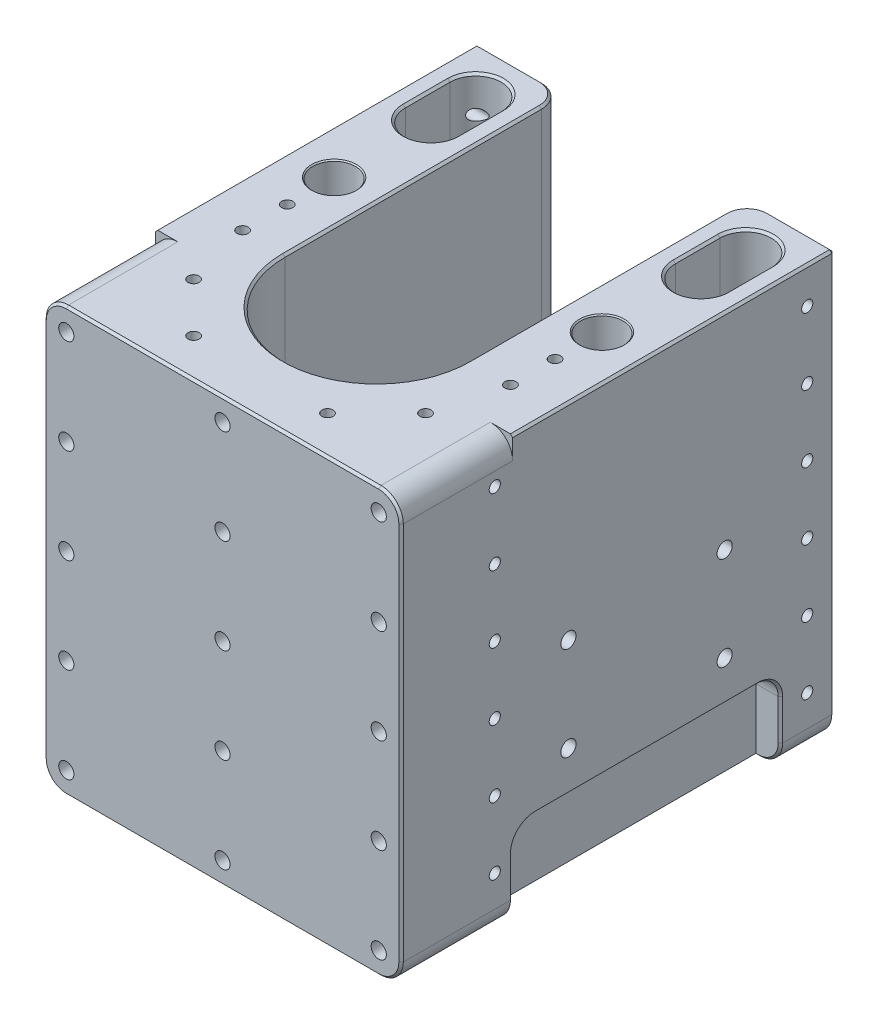
SolidWorks part; units mm, degrees
material "6061-T6 Aluminum"
ref_plane "Front Plane" through (0, 0, 0) normal (0, 0, 1) x (1, 0, 0)
ref_plane "Top Plane" through (0, 0, 0) normal (0, 1, 0) x (1, 0, 0)
ref_plane "Right Plane" through (0, 0, 0) normal (1, 0, 0) x (0, 0, -1)
sketch "Sketch1" plane through (0, 0, 0) normal (0, 1, 0) x (1, 0, 0)
  line L0 (41, 97) -> (80, 97)
  line L1 (-80, -97) -> (80, -97)
  line L2 (-80, -97) -> (-80, 97)
  line L3 (-80, 97) -> (-41, 97)
  line L4 (80, -97) -> (80, 97)
  line L5 (-41, 97) -> (0, 97) construction
  line L6 (0, 97) -> (41, 97) construction
  line L7 (-41, 97) -> (-41, -28)
  line L9 (41, -28) -> (41, 97)
  line L10 (-80, 0) -> (0, 0) construction
  line L11 (0, 0) -> (80, 0) construction
  line L12 (0, -69) -> (0, -97) construction
  arc A2 (-41, -28) -> (41, -28) centre (0, -28) ccw
  point P0 (0, 0)
  dimension "D1" = 160
  dimension "D2" = 194
  dimension "D3" = 28
  dimension "D4" = 82
extrude "Boss-Extrude1" add sketch "Sketch1" along normal blind 190
sketch "Sketch3" plane through (0, 190, 0) normal (0, 1, 0) x (1, 0, 0)
  line L0 (0, 0) -> (0, 13) construction
  line L3 (-60, 13) -> (60, 13) construction
  circle A4 centre (-60, 13) radius 9.55
  circle A5 centre (60, 13) radius 9.55
  dimension "D1" = 13
  dimension "D2" = 120
  dimension "D3" = 19.1
extrude "Cut-Extrude2" cut sketch "Sketch3" against normal blind 20 contours A4 | A5 region at (-60, 190, -13) region at (60, 190, -13)
sketch "Sketch8" plane through (80, 0, 0) normal (1, 0, 0) x (0, 0, -1)
  arc A0 (48, 102.25) -> (48, 93.75) centre (48, 98) ccw construction
  arc A1 (-22, 102.25) -> (-22, 93.75) centre (-22, 98) ccw construction
  arc A2 (-22, 60.25) -> (-22, 51.75) centre (-22, 56) ccw construction
  arc A3 (48, 60.25) -> (48, 51.75) centre (48, 56) ccw construction
  arc A4 (48, 102.25) -> (48, 93.75) centre (48, 98) ccw construction
  arc A5 (-22, 102.25) -> (-22, 93.75) centre (-22, 98) ccw construction
  arc A6 (-22, 60.25) -> (-22, 51.75) centre (-22, 56) ccw construction
  arc A7 (48, 60.25) -> (48, 51.75) centre (48, 56) ccw construction
hole_wizard "M8x1.25 Tapped Hole1" positions "Sketch11" profile "Sketch10" tap size "M8x1.25" standard "ANSI Metric"
sketch "Sketch11" plane through (80, 0, 0) normal (1, 0, 0) x (0, 0, -1)
  point P0 (48, 56)
  point P3 (-22, 56)
  point P6 (-22, 98)
  point P9 (48, 98)
cosmetic thread "Hole Thread2" parameters "D1"=25, "D2"=8
cosmetic thread "Hole Thread3" parameters "D1"=25, "D2"=8
cosmetic thread "Hole Thread4" parameters "D1"=25, "D2"=8
cosmetic thread "Hole Thread5" parameters "D1"=25, "D2"=8
sketch "Sketch10" plane through (80, 56, -48) normal (0, 1, 0) x (0, 0, -1)
  line L0 (0, 0) -> (0, 32.0429)
  line L1 (0, 32.0429) -> (3.4, 30)
  line L2 (3.4, 30) -> (3.4, 0)
  line L5 (3.4, 0) -> (0, 0)
  line L10 (0, 32.0429) -> (-3.4, 30) construction
  line L11 (0, -6.35) -> (0, 107.95) construction
  dimension "Tap Drill Dia." = 6.8
  dimension "Tap Drill Depth" = 30
  dimension "Drill Angle" = 118
mirror "Mirror2" about plane through (0, 0, 0) normal (1, 0, 0) of "M8x1.25 Tapped Hole1"
sketch "Sketch33" plane through (0, 0, 97) normal (0, 0, 1) x (1, 0, 0)
  line L0 (-80, 190) -> (-80, 0) construction
  line L1 (-70, 0) -> (70, 0)
  line L2 (-80, 10) -> (-80, 180)
  line L3 (-70, 190) -> (70, 190)
  line L4 (80, 10) -> (80, 180)
  line L5 (-70, 137.5) -> (-70, 95) construction
  line L6 (-70, 180) -> (-70, 137.5) construction
  line L7 (-70, 95) -> (-70, 52.5) construction
  line L8 (-70, 52.5) -> (-70, 10) construction
  line L9 (-80, 190) -> (80, 190) construction
  arc A0 (-70, 0) -> (-80, 10) centre (-70, 10) cw
  arc A1 (70, 0) -> (80, 10) centre (70, 10) ccw
  arc A2 (70, 190) -> (80, 180) centre (70, 180) cw
  arc A3 (-80, 180) -> (-70, 190) centre (-70, 180) cw
  circle A4 centre (-70, 180) radius 3.375
  circle A5 centre (-70, 137.5) radius 3.375
  circle A7 centre (-70, 95) radius 3.375
  circle A8 centre (-70, 10) radius 3.375
  circle A9 centre (-70, 52.5) radius 3.375
  circle A10 centre (0, 180) radius 3.375
  circle A11 centre (70, 180) radius 3.375
  circle A12 centre (0, 137.5) radius 3.375
  circle A13 centre (70, 137.5) radius 3.375
  circle A14 centre (0, 95) radius 3.375
  circle A15 centre (70, 95) radius 3.375
  circle A16 centre (0, 52.5) radius 3.375
  circle A17 centre (70, 52.5) radius 3.375
  circle A18 centre (70, 10) radius 3.375
  circle A19 centre (0, 10) radius 3.375
  point P5 (-80, 128)
  dimension "D2" = 10
  dimension "D3" = 6.75
fillet "Fillet1" radius 10 2 edges at (41, 95, -97) (-41, 95, -97)
sketch "Sketch36" plane through (0, 0, 0) normal (0, 1, 0) x (1, 0, 0)
  line L0 (-69, 13) -> (0, 13) construction
  line L1 (-102.762, 73) -> (-69, 73)
  line L2 (-102.762, 73) -> (-102.762, -47)
  line L3 (-102.762, -47) -> (-69, -47)
  line L4 (-69, 73) -> (-69, -47)
  line L5 (122.5295, 73) -> (69, 73)
  line L6 (122.5295, 73) -> (122.5295, -47)
  line L7 (122.5295, -47) -> (69, -47)
  line L8 (69, 73) -> (69, -47)
  line L9 (0, 13) -> (69, 13) construction
  line L10 (-80, -18.6) -> (-80, -25.4) construction
  line L11 (-80, 51.4) -> (-80, 44.6) construction
  line L12 (-80, -18.6) -> (-80, -25.4) construction
  line L13 (-80, 51.4) -> (-80, 44.6) construction
  line L14 (-80, 44.6) -> (-69, 13) construction
  line L15 (-69, 13) -> (-80, -18.6) construction
  line L16 (0, 13) -> (0, 0) construction
  dimension "D1" = 138
  dimension "D2" = 120
extrude "Cut-Extrude3" cut sketch "Sketch36" along normal blind 38
hole_wizard "CBORE for M8 SHCS1" positions "Sketch31" profile "Sketch32" counterbore size "M8" standard "ANSI Metric" end condition through all
sketch "Sketch31" plane through (0, 0, 0) normal (0, -1, 0) x (-1, 0, 0)
  circle A4 centre (60, 13) radius 9.55 construction
  circle A5 centre (-60, 13) radius 9.55 construction
  point P0 (60, 13)
  point P2 (-60, 13)
sketch "Sketch32" plane through (-60, 0, -13) normal (1, 0, 0) x (0, 0, -1)
  line L0 (0, 0) -> (0, 190)
  line L1 (0, 190) -> (4.5, 190)
  line L3 (4.5, 190) -> (4.5, 9)
  line L4 (4.5, 9) -> (7.5, 9)
  line L5 (7.5, 9) -> (7.5, 0)
  line L7 (7.5, 0) -> (0, 0)
  line L11 (0, -6.35) -> (0, 107.95) construction
  dimension "Thru Hole Dia." = 9
  dimension "Thru Hole Depth" = 190
  dimension "C'Bore Dia." = 15
  dimension "C'Bore Depth" = 9
chamfer "Chamfer7" distance 0.5 angle 45 2 edges at (60, 190, -3.45) (-60, 190, -3.45)
chamfer "Chamfer11" distance 1 angle 45 2 edges at (60, 0, -20.5) (-60, 0, -20.5)
chamfer "Chamfer12" distance 0.5 angle 45 4 edges at (-60, 9, -17.5) (60, 9, -17.5) (-60, 170, -8.5) (60, 170, -8.5)
sketch "Sketch38" plane through (0, 0, 0) normal (0, -1, 0) x (1, 0, 0)
  circle A0 centre (54, 32.5) radius 4.25 construction
  circle A1 centre (54, 2.5) radius 4.25 construction
  circle A2 centre (54, -27.5) radius 4.25 construction
  circle A3 centre (54, -57.5) radius 4.25 construction
  circle A4 centre (-54, -57.5) radius 4.25 construction
  circle A5 centre (-54, -27.5) radius 4.25 construction
  circle A6 centre (-54, 2.5) radius 4.25 construction
  circle A7 centre (-54, 32.5) radius 4.25 construction
  circle A8 centre (54, 32.5) radius 4.25
  circle A9 centre (54, 2.5) radius 4.25
  circle A10 centre (54, -27.5) radius 4.25
  circle A11 centre (54, -57.5) radius 4.25
  circle A12 centre (-54, -57.5) radius 4.25
  circle A13 centre (-54, -27.5) radius 4.25
  circle A14 centre (-54, 2.5) radius 4.25
  circle A15 centre (-54, 32.5) radius 4.25
sketch "Sketch39" plane through (0, 0, 0) normal (0, -1, 0) x (-1, 0, 0)
  line L0 (-54, -2.5) -> (-54, -32.5) construction
  line L1 (-54, -32.5) -> (-54, -62.5) construction
  line L3 (54, -2.5) -> (54, -32.5) construction
  line L4 (54, -32.5) -> (54, -62.5) construction
  point P0 (54, 57.5)
  point P3 (54, 27.5)
  point P6 (54, -2.5)
  point P9 (54, -32.5)
  point P12 (-54, 57.5)
  point P15 (-54, 27.5)
  point P18 (-54, -2.5)
  point P21 (-54, -32.5)
  point P36 (-54, -62.5)
  point P39 (54, -62.5)
hole_wizard "M8x1.25 Tapped Hole3" positions "Sketch39" profile "Sketch40" tap size "M8x1.25" standard "ANSI Metric"
sketch "Sketch40" plane through (-54, 0, -57.5) normal (1, 0, 0) x (0, 0, -1)
  line L0 (0, 0) -> (0, 22.0429)
  line L1 (0, 22.0429) -> (3.4, 20)
  line L2 (3.4, 20) -> (3.4, 0.9)
  line L3 (3.4, 0.9) -> (4.3, 0)
  line L5 (4.3, 0) -> (0, 0)
  line L6 (-3.4, 0.9) -> (-4.3, 0) construction
  line L10 (0, 22.0429) -> (-3.4, 20) construction
  line L11 (0, -6.35) -> (0, 107.95) construction
  dimension "Tap Drill Dia." = 6.8
  dimension "Tap Drill Depth" = 20
  dimension "Near C'Sink Dia." = 8.6
  dimension "Near C'Sink Angle" = 90
  dimension "Drill Angle" = 118
cosmetic thread "Hole Thread36" parameters "D1"=16, "D2"=8
cosmetic thread "Hole Thread37" parameters "D1"=16, "D2"=8
cosmetic thread "Hole Thread38" parameters "D1"=16, "D2"=8
cosmetic thread "Hole Thread39" parameters "D1"=16, "D2"=8
cosmetic thread "Hole Thread40" parameters "D1"=16, "D2"=8
cosmetic thread "Hole Thread41" parameters "D1"=16, "D2"=8
cosmetic thread "Hole Thread42" parameters "D1"=16, "D2"=8
cosmetic thread "Hole Thread43" parameters "D1"=16, "D2"=8
cosmetic thread "Hole Thread48" parameters "D1"=16, "D2"=8
cosmetic thread "Hole Thread49" parameters "D1"=16, "D2"=8
sketch "Sketch41" plane through (0, 0, 0) normal (0, -1, 0) x (1, 0, 0)
  line L0 (-60, 85) -> (-20, 85) construction
  line L1 (-20, 85) -> (20, 85) construction
  line L2 (20, 85) -> (60, 85) construction
  line L3 (0, 85) -> (0, -13) construction
  line L5 (-60, 85) -> (-60, 65.3183) construction
  circle A0 centre (-60, 85) radius 2.5
  circle A1 centre (-20, 85) radius 2.5
  circle A2 centre (20, 85) radius 2.5
  circle A3 centre (60, 85) radius 2.5
  point P13 (0, 87.5034)
  dimension "D2" = 5
  dimension "D1" = 40
  dimension "D3" = 85
sketch "Sketch42" plane through (0, 0, 0) normal (0, -1, 0) x (-1, 0, 0)
sketch "Sketch44" plane through (0, 0, 0) normal (0, -1, 0) x (-1, 0, 0)
  point P0 (-60, -85)
  point P3 (-20, -85)
  point P6 (20, -85)
  point P9 (60, -85)
hole_wizard "M6x1.0 Tapped Hole1" positions "Sketch44" profile "Sketch43" tap size "M6x1.0" standard "ANSI Metric"
sketch "Sketch43" plane through (60, 0, 85) normal (1, 0, 0) x (0, 0, -1)
  line L0 (0, 0) -> (0, 16.5022)
  line L1 (0, 16.5022) -> (2.5, 15)
  line L2 (2.5, 15) -> (2.5, 0.525)
  line L3 (2.5, 0.525) -> (3.025, 0)
  line L5 (3.025, 0) -> (0, 0)
  line L6 (-2.5, 0.525) -> (-3.025, 0) construction
  line L10 (0, 16.5022) -> (-2.5, 15) construction
  line L11 (0, -6.35) -> (0, 107.95) construction
  dimension "Tap Drill Dia." = 5
  dimension "Tap Drill Depth" = 15
  dimension "Near C'Sink Dia." = 6.05
  dimension "Near C'Sink Angle" = 90
  dimension "Drill Angle" = 118
cosmetic thread "Hole Thread44" parameters "D1"=12, "D2"=6
cosmetic thread "Hole Thread45" parameters "D1"=12, "D2"=6
cosmetic thread "Hole Thread46" parameters "D1"=12, "D2"=6
cosmetic thread "Hole Thread47" parameters "D1"=12, "D2"=6
sketch "Sketch45" plane through (0, 190, 0) normal (0, 1, 0) x (1, 0, 0)
  line L0 (-60.5, 56.9051) -> (-60.5, 76.9051) construction
  line L1 (-72, 56.9051) -> (-72, 76.9051)
  line L2 (-49, 56.9051) -> (-49, 76.9051)
  arc A0 (-72, 56.9051) -> (-49, 56.9051) centre (-60.5, 56.9051) ccw
  arc A1 (-49, 76.9051) -> (-72, 76.9051) centre (-60.5, 76.9051) ccw
  point P2 (-60.5, 66.9051)
  point P11 (-60.5, 78.5424)
  point P12 (-60, 51.8453)
  point P13 (-60.5, 66.9051)
  dimension "D3" = 20
extrude "Cut-Extrude4" cut sketch "Sketch45" against normal blind 25
mirror "Mirror3" about plane through (0, 0, 0) normal (1, 0, 0) of "Cut-Extrude4"
fillet "Fillet2" radius 10 4 edges at (74.5, 38, 47) (74.5, 38, -73) (-74.5, 38, 47) (-74.5, 38, -73)
sketch "Sketch46" plane through (0, 0, 97) normal (0, 0, 1) x (1, 0, 0)
  line L0 (-80, 190) -> (80, 190) construction
  line L1 (80, 190) -> (80, 0) construction
  line L2 (70, 190) -> (80, 190)
  line L3 (80, 190) -> (80, 180)
  arc A0 (70, 190) -> (80, 180) centre (70, 180) cw
  point P7 (80, 126.8989)
  dimension "D1" = 10
extrude "Cut-Extrude5" cut sketch "Sketch46" against normal blind 50
mirror "Mirror4" about plane through (0, 0, 0) normal (1, 0, 0) of "Cut-Extrude5"
fillet "Fillet3" radius 10 4 edges at (-80, 0, -85) (80, 0, -85) (80, 0, 72) (-80, 0, 72)
chamfer "Chamfer3" distance 1 angle 45 28 edges at (80, 190, -25) (80, 95, 97) (-60.5, 0, -97) (-80, 95, 97) (-80, 190, -25) (-65.5, 190, -97) (-80, 100, -97) (0, 190, 97) (60.5, 0, -97) (65.5, 190, -97) (43.9289, 0, -94.0711) (43.9289, 190, -94.0711) (41, 0, -29.5) (41, 190, -29.5) (0, 0, 69) (0, 190, 69) (-41, 0, -29.5) (-41, 190, -29.5) (-43.9289, 0, -94.0711) (-43.9289, 190, -94.0711) (0, 0, 97) (80, 100, -97) (77.0711, 187.0711, 97) (77.0711, 2.9289, 97) (-77.0711, 187.0711, 97) (-77.0711, 2.9289, 97) (77.0711, 2.9289, -97) (-77.0711, 2.9289, -97)
chamfer "Chamfer15" distance 1 angle 45 8 edges at (49, 190, -66.9051) (60.5, 190, -88.4051) (60.5, 190, -45.4051) (72, 190, -66.9051) (-72, 190, -66.9051) (-60.5, 190, -45.4051) (-60.5, 190, -88.4051) (-49, 190, -66.9051)
chamfer "Chamfer16" distance 1 angle 45 20 edges at (-69, 0, -13) (69, 0, -13) (-77.0711, 2.9289, -73) (-77.0711, 2.9289, 47) (-80, 19, -73) (-80, 19, 47) (-80, 35.0711, -70.0711) (-80, 35.0711, 44.0711) (-80, 38, -13) (77.0711, 2.9289, 47) (80, 19, 47) (80, 35.0711, 44.0711) (80, 38, -13) (77.0711, 2.9289, -73) (80, 35.0711, -70.0711) (80, 19, -73) (-69.5, 0, -73) (-69.5, 0, 47) (69.5, 0, 47) (69.5, 0, -73)
hole_wizard "M8x1.25 Tapped Hole4" positions "Sketch47" profile "Sketch48" tap size "M8x1.25" standard "ANSI Metric"
sketch "Sketch47" plane through (0, 0, 97) normal (0, 0, 1) x (1, 0, 0)
  point P0 (-70, 180)
  point P3 (0, 180)
  point P6 (70, 180)
  point P9 (70, 137.5)
  point P12 (70, 95)
  point P15 (70, 52.5)
  point P18 (70, 10)
  point P21 (0, 137.5)
  point P24 (0, 95)
  point P27 (0, 52.5)
  point P30 (0, 10)
  point P33 (-70, 137.5)
  point P36 (-70, 95)
  point P39 (-70, 52.5)
  point P42 (-70, 10)
sketch "Sketch48" plane through (-70, 180, 97) normal (1, 0, 0) x (0, -1, 0)
  line L0 (0, 0) -> (0, 22.0429)
  line L1 (0, 22.0429) -> (3.4, 20)
  line L2 (3.4, 20) -> (3.4, 0)
  line L5 (3.4, 0) -> (0, 0)
  line L10 (0, 22.0429) -> (-3.4, 20) construction
  line L11 (0, -6.35) -> (0, 107.95) construction
  dimension "Tap Drill Dia." = 6.8
  dimension "Tap Drill Depth" = 20
  dimension "Drill Angle" = 118
cosmetic thread "Hole Thread50" parameters "D1"=16, "D2"=8
cosmetic thread "Hole Thread51" parameters "D1"=16, "D2"=8
cosmetic thread "Hole Thread52" parameters "D1"=16, "D2"=8
cosmetic thread "Hole Thread53" parameters "D1"=16, "D2"=8
cosmetic thread "Hole Thread54" parameters "D1"=16, "D2"=8
cosmetic thread "Hole Thread55" parameters "D1"=16, "D2"=8
cosmetic thread "Hole Thread56" parameters "D1"=16, "D2"=8
cosmetic thread "Hole Thread57" parameters "D1"=16, "D2"=8
cosmetic thread "Hole Thread58" parameters "D1"=16, "D2"=8
cosmetic thread "Hole Thread59" parameters "D1"=16, "D2"=8
cosmetic thread "Hole Thread60" parameters "D1"=16, "D2"=8
cosmetic thread "Hole Thread61" parameters "D1"=16, "D2"=8
cosmetic thread "Hole Thread62" parameters "D1"=16, "D2"=8
cosmetic thread "Hole Thread63" parameters "D1"=16, "D2"=8
cosmetic thread "Hole Thread64" parameters "D1"=16, "D2"=8
sketch "Sketch49" plane through (0, 190, 0) normal (0, 1, 0) x (1, 0, 0)
  line L0 (60, -8) -> (60, -28) construction
  line L1 (60, -28) -> (51.9615, -58) construction
  line L2 (51.9615, -58) -> (30, -79.9615) construction
  line L3 (30, -79.9615) -> (0, -88) construction
  circle A0 centre (0, -28) radius 60 construction
  circle A1 centre (0, -88) radius 3
  circle A2 centre (30, -79.9615) radius 3
  circle A3 centre (51.9615, -58) radius 3
  circle A4 centre (60, -28) radius 3
  circle A5 centre (60, -8) radius 3
  circle A6 centre (-30, -79.9615) radius 3
  circle A7 centre (-51.9615, -58) radius 3
  circle A8 centre (-60, -28) radius 3
  circle A9 centre (-60, -8) radius 3
  point P21 (0, 0)
  point P22 (0, 0)
  point P23 (0, 0)
  point P24 (0, 0)
  dimension "D1" = 120
  dimension "D3" = 6
  dimension "D2" = 20
  dimension "D4" = 20
hole_wizard "M6x1.0 Tapped Hole2" positions "Sketch50" profile "Sketch51" tap size "M6x1.0" standard "ANSI Metric"
sketch "Sketch50" plane through (0, 190, 0) normal (0, 1, 0) x (1, 0, 0)
  point P0 (-60, -8)
  point P3 (-60, -28)
  point P6 (-51.9615, -58)
  point P9 (-30, -79.9615)
  point P12 (30, -79.9615)
  point P15 (51.9615, -58)
  point P18 (60, -28)
  point P21 (60, -8)
sketch "Sketch51" plane through (-60, 190, 8) normal (1, 0, 0) x (0, 0, 1)
  line L0 (0, 0) -> (0, 18.5022)
  line L1 (0, 18.5022) -> (2.5, 17)
  line L2 (2.5, 17) -> (2.5, 0)
  line L5 (2.5, 0) -> (0, 0)
  line L10 (0, 18.5022) -> (-2.5, 17) construction
  line L11 (0, -6.35) -> (0, 107.95) construction
  dimension "Tap Drill Dia." = 5
  dimension "Tap Drill Depth" = 17
  dimension "Drill Angle" = 118
cosmetic thread "Hole Thread65" parameters "D1"=12, "D2"=6
cosmetic thread "Hole Thread66" parameters "D1"=12, "D2"=6
cosmetic thread "Hole Thread67" parameters "D1"=12, "D2"=6
cosmetic thread "Hole Thread68" parameters "D1"=12, "D2"=6
cosmetic thread "Hole Thread69" parameters "D1"=12, "D2"=6
cosmetic thread "Hole Thread70" parameters "D1"=12, "D2"=6
cosmetic thread "Hole Thread71" parameters "D1"=12, "D2"=6
cosmetic thread "Hole Thread72" parameters "D1"=12, "D2"=6
sketch "Sketch52" plane through (-80, 0, 0) normal (-1, 0, 0) x (0, 0, 1)
  line L0 (55, 174) -> (55, 144) construction
  line L1 (55, 144) -> (55, 114) construction
  line L2 (55, 114) -> (55, 84) construction
  line L3 (-85, 174) -> (-85, 144) construction
  line L4 (-85, 144) -> (-85, 114) construction
  line L5 (-85, 114) -> (-85, 84) construction
  line L6 (-95, 583.6774) -> (-95, -14.3701) construction
  line L8 (65, 581.1581) -> (65, -30.1697) construction
  line L10 (55, 174) -> (55, 190) construction
  line L11 (47, 190) -> (96, 190) construction
  line L12 (55, 84) -> (55, 54) construction
  line L13 (55, 54) -> (55, 24) construction
  circle A0 centre (-85, 174) radius 3
  circle A1 centre (-85, 144) radius 3
  circle A2 centre (-85, 114) radius 3
  circle A3 centre (-85, 84) radius 3
  circle A4 centre (55, 174) radius 3
  circle A5 centre (55, 144) radius 3
  circle A6 centre (55, 114) radius 3
  circle A7 centre (55, 84) radius 3
  circle A8 centre (55, 54) radius 3
  circle A9 centre (55, 24) radius 3
  circle A10 centre (-85, 54) radius 3
  circle A11 centre (-85, 24) radius 3
  dimension "D1" = 6
  dimension "D2" = 10
  dimension "D3" = 10
  dimension "D4" = 30
  dimension "D5" = 16
hole_wizard "M6x1.0 Tapped Hole3" positions "Sketch53" profile "Sketch54" tap size "M6x1.0" standard "ANSI Metric"
sketch "Sketch53" plane through (-80, 0, 0) normal (-1, 0, 0) x (0, 0, 1)
  point P0 (-85, 174)
  point P3 (-85, 144)
  point P6 (-85, 114)
  point P9 (-85, 84)
  point P12 (55, 174)
  point P15 (55, 144)
  point P18 (55, 114)
  point P21 (55, 84)
  point P25 (-85, 54)
  point P28 (-85, 24)
  point P31 (55, 54)
  point P34 (55, 24)
sketch "Sketch54" plane through (-80, 174, -85) normal (0, 1, 0) x (0, 0, 1)
  line L0 (0, 0) -> (0, 18.5022)
  line L1 (0, 18.5022) -> (2.5, 17)
  line L2 (2.5, 17) -> (2.5, 0)
  line L5 (2.5, 0) -> (0, 0)
  line L10 (0, 18.5022) -> (-2.5, 17) construction
  line L11 (0, -6.35) -> (0, 107.95) construction
  dimension "Tap Drill Dia." = 5
  dimension "Tap Drill Depth" = 17
  dimension "Drill Angle" = 118
cosmetic thread "Hole Thread73" parameters "D1"=12, "D2"=6
cosmetic thread "Hole Thread74" parameters "D1"=12, "D2"=6
cosmetic thread "Hole Thread75" parameters "D1"=12, "D2"=6
cosmetic thread "Hole Thread76" parameters "D1"=12, "D2"=6
cosmetic thread "Hole Thread77" parameters "D1"=12, "D2"=6
cosmetic thread "Hole Thread78" parameters "D1"=12, "D2"=6
cosmetic thread "Hole Thread79" parameters "D1"=12, "D2"=6
cosmetic thread "Hole Thread80" parameters "D1"=12, "D2"=6
cosmetic thread "Hole Thread81" parameters "D1"=12, "D2"=6
cosmetic thread "Hole Thread82" parameters "D1"=12, "D2"=6
cosmetic thread "Hole Thread83" parameters "D1"=12, "D2"=6
cosmetic thread "Hole Thread84" parameters "D1"=12, "D2"=6
mirror "Mirror5" about plane through (0, 0, 0) normal (1, 0, 0) of "M6x1.0 Tapped Hole3"
